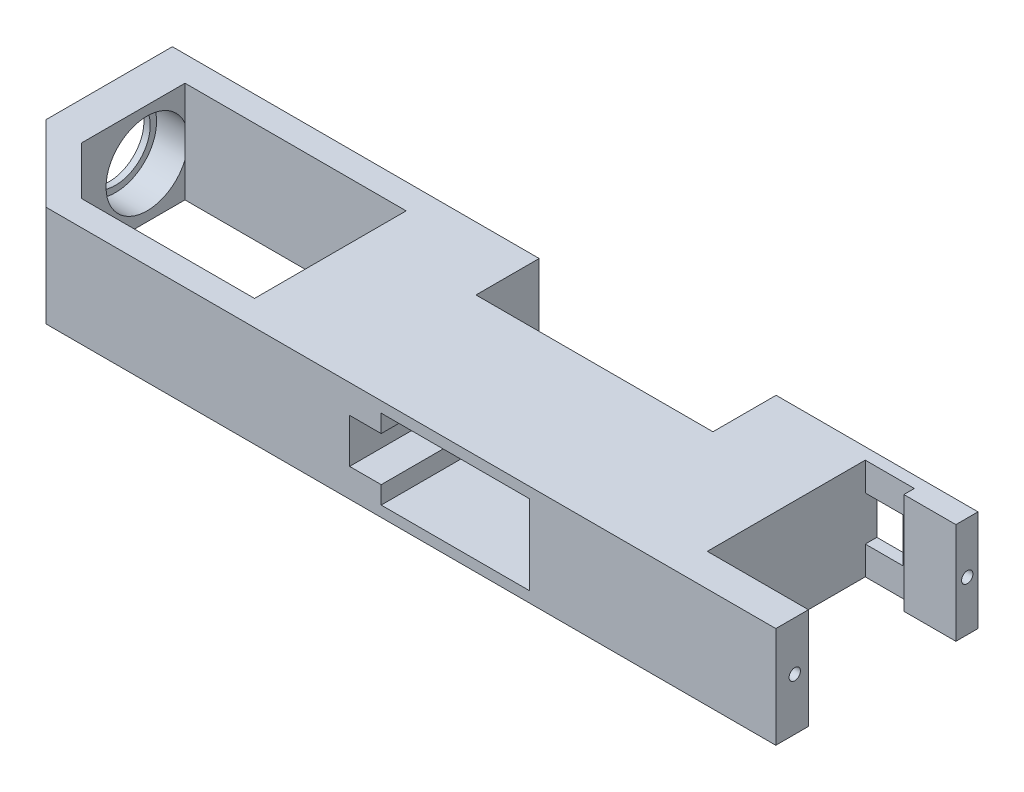
SolidWorks part; units mm, degrees
ref_plane "Front Plane" through (0, 0, 0) normal (0, 0, 1) x (1, 0, 0)
ref_plane "Top Plane" through (0, 0, 0) normal (0, 1, 0) x (1, 0, 0)
ref_plane "Right Plane" through (0, 0, 0) normal (1, 0, 0) x (0, 0, -1)
ref_axis "Axis1" through (8.5, 0, 50) along (0, 0, -1)
ref_axis "Axis2" through (88.99, 0, 0) along (-1, 0, 0)
sketch "Sketch1" plane through (0, 0, 0) normal (0, 1, 0) x (1, 0, 0)
  line L0 (64, -16.836) -> (47.9935, -16.836)
  line L1 (-63.5, 10) -> (64, 10)
  line L2 (-63.5, 10) -> (-63.5, -10)
  line L3 (-51.5, -22) -> (64, -22)
  line L4 (64, 10) -> (64, 6.5)
  line L5 (47.9935, -16.836) -> (47.9935, 8.164)
  line L6 (-63.5, -10) -> (-51.5, -22)
  line L8 (47.9935, 8.164) -> (55.7639, 8.164)
  line L9 (55.7639, 8.164) -> (55.7639, 6.5)
  line L10 (55.7639, 6.5) -> (64, 6.5)
  line L11 (64, -16.836) -> (64, -22)
  point P2 (-63.5, 0)
  dimension "D1" = 127.5
  dimension "D2" = 32
  dimension "D3" = 20
  dimension "D4" = 63.5
  dimension "D5" = 45
  dimension "D6" = 5.164
  dimension "D7" = 16.0065
  dimension "D8" = 25
  dimension "D9" = 3.5
  dimension "D10" = 8.2361
extrude "Boss-Extrude1" add sketch "Sketch1" along normal blind 8 and the other way blind 8
sketch "Sketch2" plane through (-63.5, 0, 0) normal (-1, 0, 0) x (0, 0, 1)
  circle A0 centre (0, 0) radius 5.5
  dimension "D1" = 11
extrude "Cut-Extrude1" cut sketch "Sketch2" against normal blind 8
sketch "Sketch3" plane through (0, 8, 0) normal (0, 1, 0) x (1, 0, 0)
  line L7 (-57.5, 6) -> (-22.5, 6)
  line L8 (-22.5, 6) -> (-22.5, -18)
  line L9 (-22.5, -18) -> (-49.8431, -18)
  line L10 (-49.8431, -18) -> (-57.5, -10.3431)
  line L11 (-57.5, -10.3431) -> (-57.5, 6)
  line L12 (-63.5, 10) -> (-63.5, -10) construction
  line L13 (-63.5, -10) -> (-51.5, -22) construction
  line L14 (64, 10) -> (-63.5, 10) construction
  line L15 (-51.5, -22) -> (64, -22) construction
  dimension "D1" = 6
  dimension "D2" = 4
  dimension "D3" = 4
  dimension "D4" = 4
  dimension "D5" = 35
extrude "Cut-Extrude2" cut sketch "Sketch3" against normal blind 16
sketch "Sketch4" plane through (-57.5, 0, 0) normal (1, 0, 0) x (0, 0, -1)
  circle A0 centre (0, 0) radius 6.5
  dimension "D1" = 13
extrude "Cut-Extrude3" cut sketch "Sketch4" against normal offset from surface (5 mm away) 1 contours A0 up to face at (-63.5, 0, 5.5)
sketch "Sketch5" plane through (0, 0, -10) normal (0, 0, -1) x (-1, 0, 0)
  line L0 (-64, 8) -> (63.5, 8) construction
  line L1 (-25.05, 6.3) -> (-1.55, 6.3)
  line L2 (-25.05, 6.3) -> (-25.05, -6.3)
  line L3 (-25.05, -6.3) -> (-1.55, -6.3)
  line L4 (-1.55, 6.3) -> (-1.55, -6.3)
  line L5 (-64, -8) -> (63.5, -8) construction
  line L6 (63.5, -8) -> (63.5, 8) construction
  dimension "D1" = 1.7
  dimension "D2" = 1.7
  dimension "D3" = 65.05
  dimension "D4" = 23.5
extrude "Cut-Extrude4" cut sketch "Sketch5" against normal through all
sketch "Sketch6" plane through (0, 0, -10) normal (0, 0, -1) x (-1, 0, 0)
  circle A0 centre (-0.2, 0) radius 0.9
  circle A1 centre (-27.5, 0) radius 0.9
  dimension "D1" = 1.8
  dimension "D2" = 1.8
extrude "Cut-Extrude5" cut sketch "Sketch6" against normal blind 17
sketch "Sketch7" plane through (0, 0, -10) normal (0, 0, -1) x (-1, 0, 0)
  line L0 (-64, -8) -> (63.5, -8) construction
  line L1 (-47.9935, 3.5) -> (-53.9935, 3.5)
  line L2 (-47.9935, 3.5) -> (-47.9935, -3.5)
  line L3 (-47.9935, -3.5) -> (-53.9935, -3.5)
  line L4 (-53.9935, 3.5) -> (-53.9935, -3.5)
  point P4 (-47.9935, 0)
  dimension "D1" = 7
  dimension "D2" = 6
  dimension "D3" = 8
  dimension "D4" = 0
extrude "Cut-Extrude6" cut sketch "Sketch7" against normal blind 7
sketch "Sketch8" plane through (0, 0, 22) normal (0, 0, 1) x (1, 0, 0)
  line L0 (1.55, -6.3) -> (1.55, 6.3) construction
  line L1 (1.55, -3.5) -> (-3.45, -3.5)
  line L2 (1.55, -3.5) -> (1.55, 3.5)
  line L3 (1.55, 3.5) -> (-3.45, 3.5)
  line L4 (-3.45, -3.5) -> (-3.45, 3.5)
  point P7 (1.55, 0)
  point P8 (1.55, 0)
  dimension "D1" = 5
  dimension "D2" = 7
extrude "Cut-Extrude7" cut sketch "Sketch8" against normal blind 10
sketch "Sketch9" plane through (64, 0, 0) normal (1, 0, 0) x (0, 0, -1)
  circle A0 centre (-18.9984, 0.247) radius 0.9
  circle A1 centre (8.2993, -0.1079) radius 0.9
  dimension "D1" = 1.8
  dimension "D2" = 1.8
extrude "Cut-Extrude8" cut sketch "Sketch9" against normal blind 7
sketch "Sketch10" plane through (0, 0, -10) normal (0, 0, -1) x (-1, 0, 0)
  line L0 (5.45, -8) -> (5.45, 8)
  line L1 (-64, -8) -> (63.5, -8) construction
  line L2 (-64, 8) -> (63.5, 8) construction
  line L3 (5.45, 8) -> (-32.05, 8)
  line L4 (-32.05, 8) -> (-32.05, -8)
  line L5 (-32.05, -8) -> (5.45, -8)
  line L6 (63.5, -8) -> (63.5, 8) construction
  line L7 (-64, -8) -> (-64, 8) construction
  dimension "D1" = 58.05
  dimension "D2" = 31.95
extrude "Cut-Extrude9" cut sketch "Sketch10" against normal blind 10
